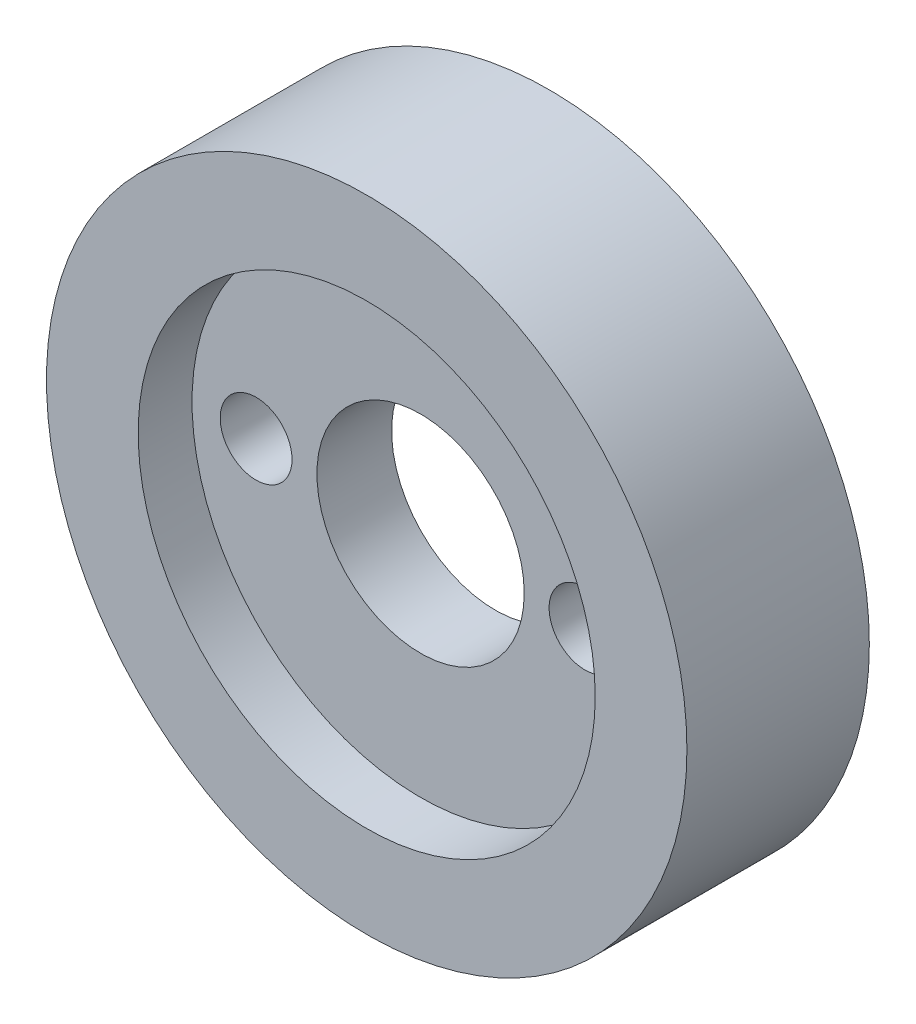
SolidWorks part; units mm, degrees
ref_plane "Front Plane" through (0, 0, 0) normal (0, 0, 1) x (1, 0, 0)
ref_plane "Top Plane" through (0, 0, 0) normal (0, 1, 0) x (1, 0, 0)
ref_plane "Right Plane" through (0, 0, 0) normal (1, 0, 0) x (0, 0, -1)
sketch "Sketch1" plane through (0, 0, 0) normal (0, 0, 1) x (1, 0, 0)
  circle A0 centre (0, 0) radius 9.8091
  circle A1 centre (0, 0) radius 3.175
  dimension "D1" = 19.6182
  dimension "D2" = 6.35
extrude "Boss-Extrude1" add sketch "Sketch1" along normal mid plane 5.588
sketch "Sketch2" plane through (0, 0, 2.794) normal (0, 0, 1) x (1, 0, 0)
  line L0 (0, 0) -> (0, 1.2313) construction
  line L1 (-7, 0) -> (-3.075, 0)
  circle A0 centre (0, 0) radius 7
  circle A1 centre (0, 0) radius 3.075
  circle A2 centre (-5.0375, 0) radius 1.1
  circle A3 centre (5.0375, 0) radius 1.1
  point P6 (-5.0375, 0)
  circle M2 centre (0, 0) radius 3.175
  dimension "D1" = 14
  dimension "D2" = 6.15
  dimension "D3" = 2.2
extrude "Cut-Extrude1" cut sketch "Sketch2" against normal blind 1.65 contours A2 A0 A3 M2 region at (0, 6.802, 2.794)
mirror "Mirror1" about plane through (0, 0, 0) normal (0, 0, 1) of "Cut-Extrude1"
extrude "Cut-Extrude2" cut sketch "Sketch2<3>" against normal through all contours L1 A2 | L1 A2 | A3 region at (-5.0375, -0.4669, 2.794) region at (-5.0375, 0.4669, 2.794) region at (5.0375, 0, 2.794)
sketch "Sketch2<3>" plane through (0, 0, 2.794) normal (0, 0, 1) x (1, 0, 0) same geometry as "Sketch2"
